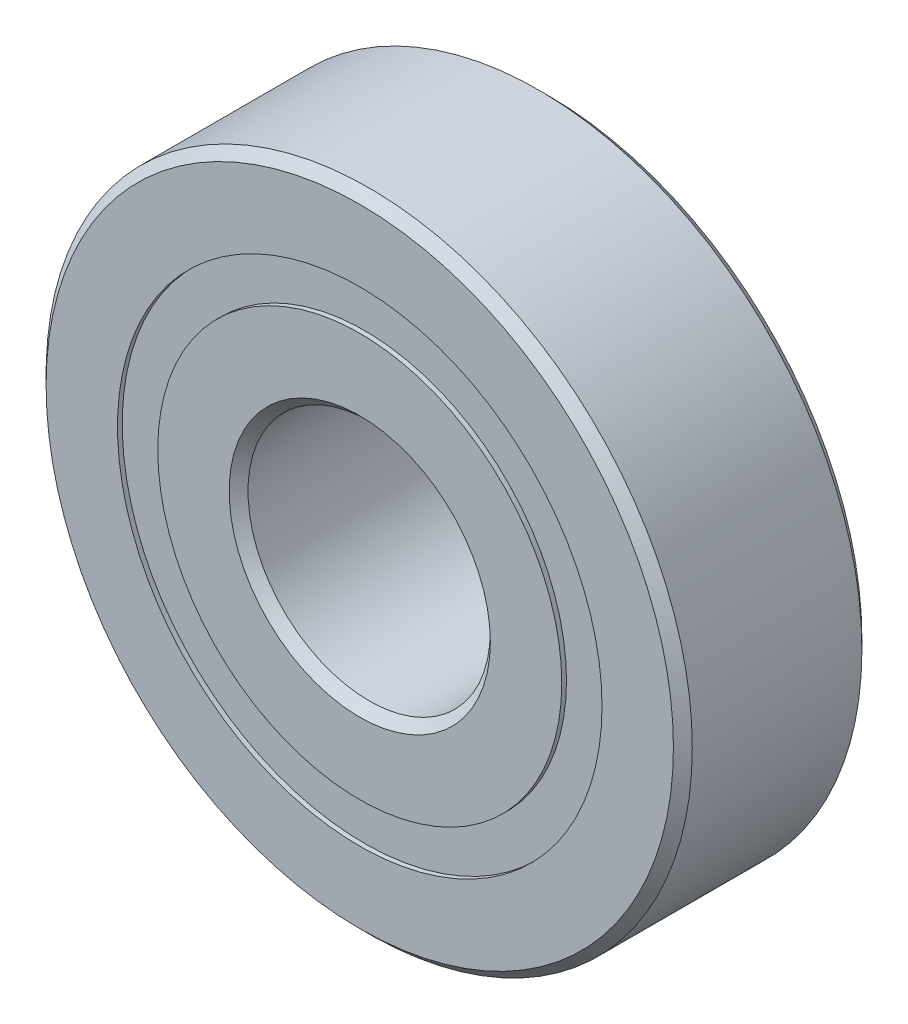
SolidWorks part; units mm, degrees
material "Alloy Steel"
ref_plane "Front Plane" through (0, 0, 0) normal (0, 0, 1) x (1, 0, 0)
ref_plane "Top Plane" through (0, 0, 0) normal (0, 1, 0) x (1, 0, 0)
ref_plane "Right Plane" through (0, 0, 0) normal (1, 0, 0) x (0, 0, -1)
sketch "Sketch1" plane through (0, 0, 0) normal (1, 0, 0) x (0, 0, -1)
  line L0 (-3.5, 0) -> (3.5, 0) construction
  line L1 (0, 12) -> (0, -12) construction
  line L2 (3.15, 12) -> (-3.15, 12)
  line L3 (-3.15, 12) -> (-3.5, 11.65)
  line L4 (-3.5, 11.65) -> (-3.5, 8.9973)
  line L5 (-3.5, 8.9973) -> (-1.5556, 8.9973)
  line L6 (3.5, 8.9973) -> (1.5556, 8.9973)
  line L7 (3.5, 11.65) -> (3.5, 8.9973)
  line L8 (3.15, 12) -> (3.5, 11.65)
  line L9 (0, 12) -> (0, 8.25) construction
  line L10 (0, 8.25) -> (0, 4.5) construction
  arc A0 (-1.5556, 8.9973) -> (1.5556, 8.9973) centre (0, 8.25) cw
  point P14 (0, 4.5)
  dimension "D3" = 3.1111
  dimension "D1" = 45
  dimension "Width" = 7
  dimension "OD" = 24
  dimension "D2" = 0.35
  dimension "Shaft Dia" = 9
  dimension "D4" = 0.7473
revolve "Revolve1" add sketch "Sketch1" angle 360 about L0
sketch "Sketch3" plane through (0, 0, 0) normal (1, 0, 0) x (0, 0, -1)
  line L0 (-3.5, 7.5027) -> (-1.5556, 7.5027)
  line L1 (0, 12) -> (0, -12) construction
  line L2 (-3.5, 11.65) -> (-3.5, 8.9973) construction
  line L3 (-3.5, 7.5027) -> (-3.5, 4.85)
  line L4 (-3.15, 12) -> (-3.5, 11.65) construction
  line L5 (-3.5, 4.85) -> (-3.15, 4.5)
  line L6 (-3.15, 4.5) -> (3.15, 4.5)
  line L7 (3.15, 12) -> (3.15, -12) construction
  line L8 (3.15, 4.5) -> (3.5, 4.85)
  line L9 (3.5, -11.65) -> (3.5, 11.65) construction
  line L10 (3.5, 4.85) -> (3.5, 7.5027)
  line L11 (3.5, 7.5027) -> (1.5556, 7.5027)
  line L13 (3.15, 12) -> (3.5, 11.65) construction
  arc A0 (1.5556, 8.9973) -> (-1.5556, 8.9973) centre (0, 8.25) ccw construction
  arc A1 (1.5556, 7.5027) -> (-1.5556, 7.5027) centre (0, 8.25) cw
revolve "Revolve3" add sketch "Sketch3" angle 360 about L0
sketch "Sketch4" plane through (0, 0, 0) normal (1, 0, 0) x (0, 0, -1)
  line L0 (-1.7257, 8.25) -> (1.7257, 8.25)
  arc A2 (-1.7257, 8.25) -> (1.7257, 8.25) centre (0, 8.25) cw
  arc A3 (1.5556, 8.9973) -> (-1.5556, 8.9973) centre (0, 8.25) ccw construction
revolve "Revolve4" add sketch "Sketch4" angle 360 about L0
ref_axis "Axis1" through (0, 0, -3.5) along (0, 0, 1)
pattern_circular "CirPattern1" count 10 every 36 about axis through (0, 0, -3.5) along (0, 0, 1) of bodies 104
sketch "Sketch5" plane through (0, 0, 0) normal (1, 0, 0) x (0, 0, -1)
  line L0 (-3.5, 8.9973) -> (-1.5556, 8.9973) construction
  line L1 (-3.325, 8.9973) -> (-1.7257, 8.9973)
  line L2 (-3.325, 8.9973) -> (-3.325, 7.5027)
  line L3 (-3.325, 7.5027) -> (-1.7257, 7.5027)
  line L4 (-1.7257, 8.9973) -> (-1.7257, 7.5027)
  line L5 (-3.5, 7.5027) -> (-1.5556, 7.5027) construction
  line L6 (3.5, 8.9973) -> (1.5556, 8.9973) construction
  line L7 (3.325, 8.9973) -> (1.7257, 8.9973)
  line L8 (3.325, 8.9973) -> (3.325, 7.5027)
  line L9 (3.325, 7.5027) -> (1.7257, 7.5027)
  line L10 (1.7257, 8.9973) -> (1.7257, 7.5027)
  line L11 (3.5, 7.5027) -> (1.5556, 7.5027) construction
  line L12 (-3.15, 12) -> (-3.5, 11.65) construction
  point P18 (-3.325, 11.825)
revolve "Revolve5" add sketch "Sketch5" angle 360 about L0
equation "\"D2@Sketch1\" = \"Width@Sketch1\"*.05"
equation "\"D3@Sketch1\" = \"Width@Sketch1\"/2.25"
equation "\"D4@Sketch1\" = (((\"OD@Sketch1\"-\"Width@Sketch1\")/2)/3.25)/3.5"
equation "\"D2@CirPattern1\" = 360/\"Balls@CirPattern1\""
